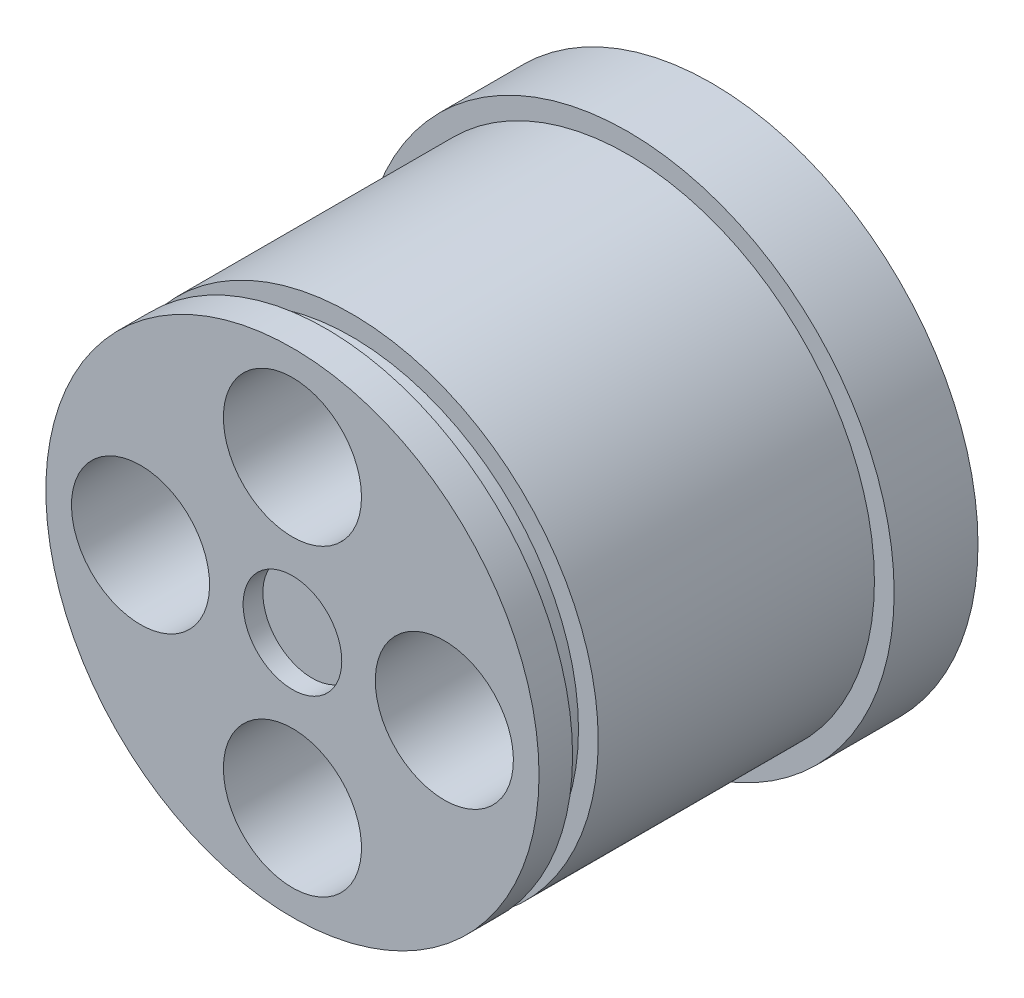
SolidWorks part; units mm, degrees
ref_plane "Front Plane" through (0, 0, 0) normal (0, 0, 1) x (1, 0, 0)
ref_plane "Top Plane" through (0, 0, 0) normal (0, 1, 0) x (1, 0, 0)
ref_plane "Right Plane" through (0, 0, 0) normal (1, 0, 0) x (0, 0, -1)
ref_axis "Z" through (0, 0, 10.5) along (0, 0, -1)
sketch "Sketch1" plane through (0, 0, 0) normal (0, 0, 1) x (1, 0, 0)
  circle A0 centre (0, 0) radius 12.5
  dimension "D1" = 25
extrude "Boss-Extrude1" add sketch "Sketch1" along normal blind 17
sketch "Sketch2" plane through (0, 0, 0) normal (0, 0, 1) x (1, 0, 0)
  circle A0 centre (0, 0) radius 13.5
  dimension "D1" = 27
extrude "Boss-Extrude2" add sketch "Sketch2" against normal blind 4.25
ref_plane "Plane1" through (0, 0, 14.65) normal (0, 0, 1) x (1, 0, 0)
sketch "Sketch3" plane through (0, 0, 14.65) normal (0, 0, 1) x (1, 0, 0)
  circle A0 centre (0, 0) radius 11.5
  circle A1 centre (0, 0) radius 58.2437
  dimension "D1" = 23
extrude "RetainingRingGroove" cut sketch "Sketch3" against normal blind 0.65 and the other way blind 0.65
sketch "Sketch4" plane through (0, 0, 17) normal (0, 0, 1) x (1, 0, 0)
  circle A0 centre (0, 0) radius 2.5
  dimension "D1" = 5
extrude "MagnetSlot" cut sketch "Sketch4" against normal blind 1
sketch "Sketch6" plane through (0, 0, 17) normal (0, 0, 1) x (1, 0, 0)
  line L0 (0, 0) -> (0, 7.7) construction
  line L2 (-1.4722, 10.25) -> (-2.9445, 7.7)
  line L3 (-2.9445, 7.7) -> (-1.4722, 5.15)
  line L4 (-1.4722, 5.15) -> (1.4722, 5.15)
  line L5 (1.4722, 5.15) -> (2.9445, 7.7)
  line L6 (2.9445, 7.7) -> (1.4722, 10.25)
  line L7 (1.4722, 10.25) -> (-1.4722, 10.25)
  circle A0 centre (0, 7.7) radius 2.55 construction
  dimension "D1" = 7.7
  dimension "D2" = 5.1
extrude "NutCut" cut sketch "Sketch6" against normal offset from surface (17.25 mm away) 4 up to face at (13.5, 0, -4.25)
sketch "Sketch7" plane through (0, 0, 17) normal (0, 0, 1) x (1, 0, 0)
  circle A0 centre (0, 7.7) radius 3.5
  dimension "D1" = 7
extrude "NutHole" cut sketch "Sketch7" against normal blind 15
sketch "Sketch8" plane through (0, 0, 17) normal (0, 0, 1) x (1, 0, 0)
  circle A0 centre (0, 7.7) radius 1.35
  dimension "D1" = 2.7
extrude "ScrewHole" cut sketch "Sketch8" against normal through all both and the other way through all
pattern_circular "CirPattern1" count 4 over 360 about axis through (0, 0, 10.5) along (0, 0, -1) of "MagnetSlot", "NutCut", "NutHole", "ScrewHole"
